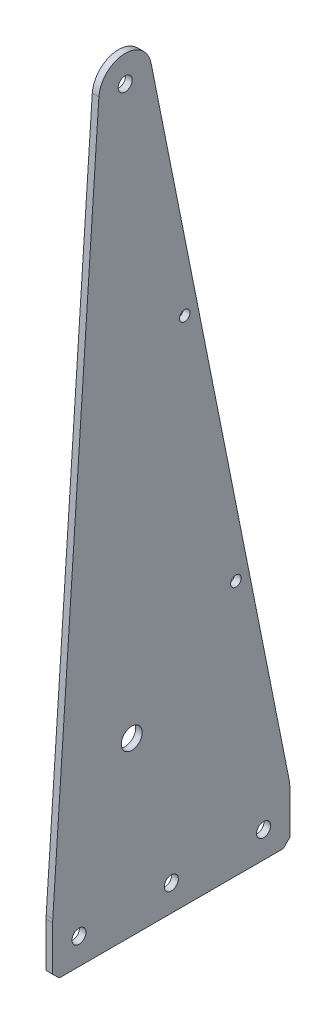
SolidWorks part; units mm, degrees
material "6061-T6 (SS)"
ref_plane "Front" through (0, 0, 0) normal (0, 0, 1) x (1, 0, 0)
ref_plane "Top" through (0, 0, 0) normal (0, 1, 0) x (1, 0, 0)
ref_plane "Right" through (0, 0, 0) normal (1, 0, 0) x (0, 0, -1)
sketch "Sketch1" plane through (0, 0, 0) normal (1, 0, 0) x (0, 0, -1)
  line L5 (63.5, 82.55) -> (-348.9452, 11.9126) construction
  line L6 (63.5, 82.55) -> (-7.1374, 494.9952) construction
  line L7 (60.3351, 357.1463) -> (22.2931, 141.3996) construction
  line L8 (22.2931, 141.3996) -> (4.6504, 41.3431) construction
  line L9 (63.5, 82.55) -> (4.6504, 41.3431) construction
  line L10 (4.6504, 41.3431) -> (-0.5288, 71.5841) construction
  line L11 (63.5, 82.55) -> (22.2931, 141.3996) construction
  line L12 (22.2931, 141.3996) -> (52.5341, 146.5788) construction
  circle A0 centre (63.5, 82.55) radius 5.0419
  dimension "D1" = 10.0838
  dimension "D3" = 63.5
  dimension "D2" = 82.55
  dimension "D4" = 80
  dimension "D7" = 70.6374
  dimension "D8" = 412.4452
  dimension "D9" = 90
  dimension "D10" = 101.6
  dimension "D11" = 219.075
sketch "Sketch2" plane through (0, 0, 0) normal (1, 0, 0) x (0, 0, -1)
  line L0 (25.4, 0) -> (25.4, 25.4)
  line L2 (25.4, 0) -> (139.7, 0)
  line L3 (139.7, 0) -> (139.7, 25.4)
  line L4 (139.7, 25.4) -> (72.788, 359.6393)
  line L6 (25.4, 25.4) -> (47.6634, 357.9945)
  arc A0 (72.788, 359.6393) -> (47.6634, 357.9945) centre (60.3351, 357.1463) ccw
  circle A2 centre (63.5, 82.55) radius 5.0419 construction
  circle A3 centre (63.5, 82.55) radius 5.0419
  circle A4 centre (60.3351, 357.1463) radius 3.3782
  dimension "D3" = 12.7
  dimension "D4" = 6.7564
  dimension "D5" = 25.4
  dimension "D1" = 25.4
  dimension "D2" = 139.7
extrude "Boss-Extrude2" add sketch "Sketch2" along normal blind 3.175
sketch "Sketch3" plane through (3.175, 0, 0) normal (1, 0, 0) x (0, 0, -1)
  line L0 (25.4, 0) -> (139.7, 0) construction
  line L1 (25.4, 25.4) -> (25.4, 0) construction
  line L2 (139.7, 0) -> (139.7, 25.4) construction
  line L3 (38.1, 12.7) -> (127, 12.7) construction
  line L4 (139.7, 25.4) -> (72.788, 359.6393) construction
  line L5 (113.6734, 123.0591) -> (89.038, 246.1182) construction
  line L6 (89.038, 246.1182) -> (64.4025, 369.1773) construction
  line L7 (113.6734, 123.0591) -> (138.3089, 0) construction
  circle A0 centre (38.1, 12.7) radius 3.3782
  circle A1 centre (82.55, 12.7) radius 3.3782
  circle A2 centre (127, 12.7) radius 3.3782
  circle A3 centre (89.038, 246.1182) radius 2.54
  circle A4 centre (113.6734, 123.0591) radius 2.54
  arc A5 (72.788, 359.6393) -> (47.6634, 357.9945) centre (60.3351, 357.1463) ccw construction
  dimension "D1" = 12.7
  dimension "D2" = 12.7
  dimension "D3" = 12.7
  dimension "D4" = 6.7564
  dimension "D5" = 6.35
  dimension "D6" = 6.35
  dimension "D7" = 5.08
extrude "Cut-Extrude1" cut sketch "Sketch3" against normal through all
chamfer "Chamfer1" distance 3.175 angle 45 2 edges at (1.5875, 0, -25.4) (1.5875, 0, -139.7)
fillet "Fillet1" radius 25.4 2 edges at (1.5875, 25.4, -139.7) (1.5875, 25.4, -25.4)
